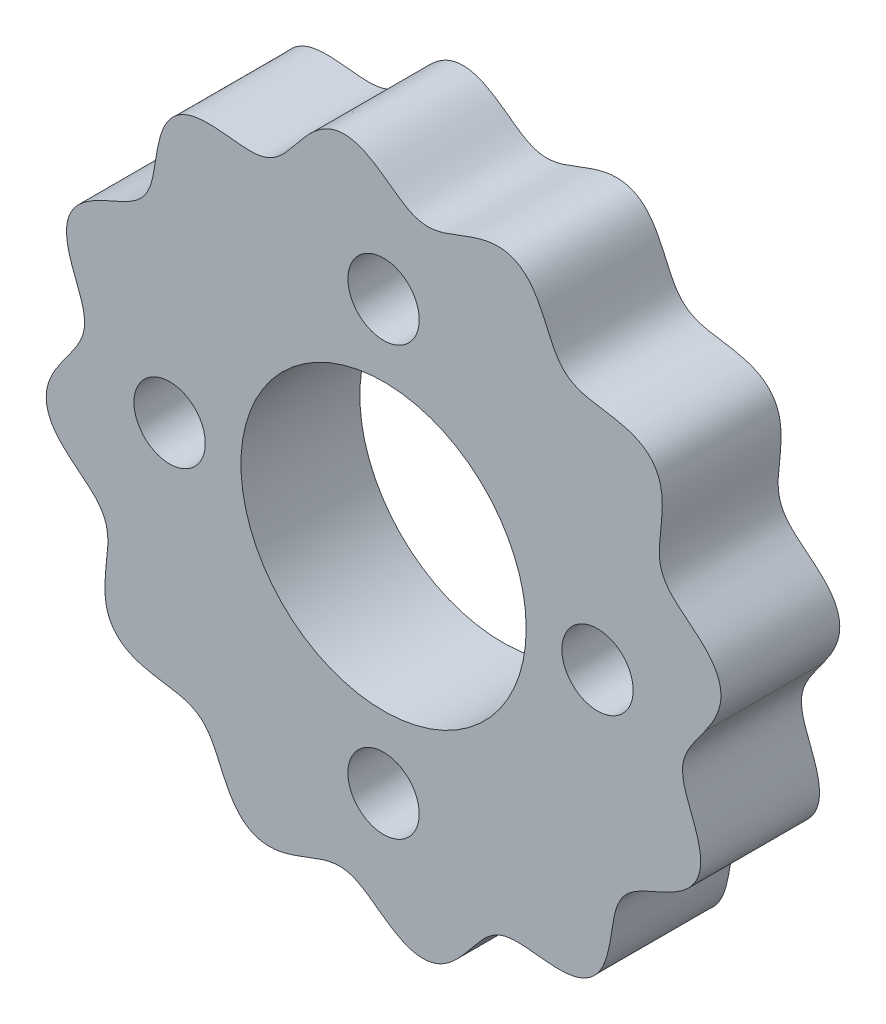
SolidWorks part; units mm, degrees
ref_plane "前视基准面" through (0, 0, 0) normal (0, 0, 1) x (1, 0, 0)
ref_plane "上视基准面" through (0, 0, 0) normal (0, 1, 0) x (1, 0, 0)
ref_plane "右视基准面" through (0, 0, 0) normal (1, 0, 0) x (0, 0, -1)
sketch "草图1" plane through (0, 0, 0) normal (0, 0, 1) x (1, 0, 0)
  circle A0 centre (0, 0) radius 12
  spline S0 degree 4 poles (26.573, -8.6341) (26.5537, -8.536) (26.5113, -8.3407) (26.4122, -7.9533) (26.2292, -7.382) (25.9846, -6.7265) (25.7182, -6.053) (25.4922, -5.4437) (25.3206, -4.8954) (25.2069, -4.4076) (25.1382, -3.8584) (25.1633, -3.2467) (25.3264, -2.6118) (25.6315, -1.9732) (25.9924, -1.3953) (26.3533, -0.8879) (26.6323, -0.5089) (26.9321, -0.0957) (27.0569, 0.0789) (27.2765, 0.396) (27.4477, 0.657) (27.6121, 0.9237) (27.7701, 1.2005) (27.9519, 1.5526) (28.1567, 2.0235) (28.3423, 2.6278) (28.4208, 3.3587) (28.3195, 4.1077) (28.0726, 4.751) (27.754, 5.2853) (27.402, 5.7395) (27.0442, 6.1277) (26.6262, 6.5264) (26.1505, 6.9354) (25.623, 7.3601) (25.0555, 7.8144) (24.5068, 8.2865) (24.0033, 8.803) (23.5859, 9.3929) (23.3119, 10.0625) (23.1946, 10.7801) (23.1899, 11.5106) (23.2475, 12.242) (23.3298, 12.9757) (23.4156, 13.786) (23.4705, 14.679) (23.4267, 15.7342) (23.1569, 16.7678) (22.6126, 17.5994) (21.8434, 18.2304) (21.0158, 18.6438) (20.1342, 18.9011) (19.2385, 19.0736) (18.4332, 19.1968) (17.7246, 19.3065) (17.0229, 19.4431) (16.3386, 19.6429) (15.6903, 19.9516) (15.1256, 20.4021) (14.6705, 20.9723) (14.3032, 21.6108) (13.9873, 22.2805) (13.6894, 22.9644) (13.3572, 23.7074) (12.9579, 24.4976) (12.3885, 25.3791) (11.6392, 26.1227) (10.7563, 26.556) (9.7906, 26.7073) (8.9022, 26.6547) (8.0357, 26.4494) (7.1919, 26.1626) (6.4375, 25.8701) (5.7603, 25.606) (5.077, 25.3667) (4.378, 25.189) (3.6584, 25.1224) (2.9416, 25.2199) (2.2614, 25.4772) (1.6264, 25.8383) (1.0219, 26.2539) (0.4276, 26.6921) (-0.2312, 27.1715) (-0.9771, 27.6656) (-1.9129, 28.1553) (-2.9429, 28.4384) (-3.9352, 28.3827) (-4.8663, 28.0321) (-5.6381, 27.5222) (-6.3017, 26.8873) (-6.8989, 26.1978) (-7.4083, 25.562) (-7.8576, 25.0032) (-8.3267, 24.4638) (-8.842, 23.9711) (-9.4335, 23.564) (-10.1059, 23.3002) (-10.8273, 23.1912) (-11.5639, 23.1923) (-12.3018, 23.2536) (-13.0431, 23.3376) (-13.8526, 23.4214) (-14.7366, 23.4706) (-15.7847, 23.4183) (-16.8033, 23.1412) (-17.6201, 22.5933) (-18.2339, 21.8325) (-18.6326, 21.0369) (-18.888, 20.1839) (-19.0615, 19.3097) (-19.1854, 18.5101) (-19.2953, 17.7915) (-19.4297, 17.0802) (-19.6253, 16.386) (-19.9274, 15.7295) (-20.3703, 15.1574) (-20.9332, 14.697) (-21.5634, 14.3277) (-22.2256, 14.0119) (-22.9022, 13.7164) (-23.6468, 13.3855) (-24.4476, 12.9866) (-25.3397, 12.421) (-26.0948, 11.6754) (-26.5388, 10.8025) (-26.7031, 9.8569) (-26.6664, 8.9884) (-26.4773, 8.1355) (-26.2027, 7.3016) (-25.9148, 6.5508) (-25.6482, 5.8708) (-25.4017, 5.1872) (-25.211, 4.4886) (-25.1244, 3.7854) (-25.1886, 3.0933) (-25.3949, 2.4518) (-25.6962, 1.8637) (-26.0443, 1.3209) (-26.3851, 0.8445) (-26.6535, 0.4799) (-26.9375, 0.0881) (-27.0592, -0.0824) (-27.2766, -0.3961) (-27.4472, -0.6562) (-27.6116, -0.9229) (-27.7695, -1.1993) (-27.9511, -1.5511) (-28.156, -2.0215) (-28.3416, -2.6252) (-28.4264, -3.4054) (-28.2941, -4.2542) (-27.9289, -5.0556) (-27.3924, -5.7762) (-26.769, -6.4074) (-26.1864, -6.9063) (-25.6744, -7.3184) (-25.3329, -7.5929) (-25.1635, -7.7318) (-25.0792, -7.8016) knots 0 0 0 0 0 0.003522 0.007043 0.014086 0.021129 0.028172 0.032574 0.036976 0.041378 0.04578 0.052068 0.058355 0.064392 0.070429 0.076467 0.079485 0.082504 0.085297 0.088091 0.090884 0.093678 0.096471 0.099265 0.104852 0.111756 0.118661 0.12494 0.131219 0.135866 0.140513 0.14516 0.149807 0.156213 0.162618 0.169024 0.175429 0.181708 0.187986 0.194329 0.200673 0.207175 0.213676 0.220178 0.22668 0.235914 0.245148 0.257333 0.263761 0.270188 0.27994 0.289691 0.29601 0.302328 0.308647 0.314965 0.321183 0.3274 0.333785 0.34017 0.346739 0.353309 0.359878 0.366447 0.375446 0.384445 0.396798 0.403077 0.409356 0.41865 0.427944 0.43435 0.440756 0.447161 0.453567 0.459845 0.466123 0.472467 0.47881 0.485312 0.491814 0.498316 0.504817 0.514051 0.523285 0.535471 0.541898 0.548326 0.558077 0.567829 0.574147 0.580466 0.586784 0.593103 0.59932 0.605538 0.611923 0.618308 0.624877 0.631446 0.638015 0.644585 0.653584 0.662583 0.674936 0.681215 0.687494 0.696788 0.706082 0.712487 0.718893 0.725299 0.731704 0.737983 0.744261 0.750604 0.756948 0.763449 0.769951 0.776453 0.782955 0.792189 0.801422 0.813608 0.819793 0.825978 0.835005 0.844032 0.850468 0.856904 0.86334 0.869776 0.876072 0.882369 0.888191 0.894014 0.899739 0.905465 0.91119 0.914053 0.916916 0.919707 0.922498 0.925289 0.928079 0.93087 0.933661 0.939243 0.946142 0.95304 0.961079 0.969118 0.976839 0.984559 0.99228 0.99614 1 1 1 1 1 construction
  spline S1 degree 4 poles (27, 0) (27.0383, 0.0539) (27.115, 0.1629) (27.2765, 0.396) (27.4477, 0.657) (27.6121, 0.9237) (27.7701, 1.2005) (27.9519, 1.5526) (28.1567, 2.0235) (28.3423, 2.6278) (28.4208, 3.3587) (28.3195, 4.1077) (28.0726, 4.751) (27.754, 5.2853) (27.402, 5.7395) (27.0442, 6.1277) (26.6262, 6.5264) (26.1505, 6.9354) (25.623, 7.3601) (25.0555, 7.8144) (24.5068, 8.2865) (24.0033, 8.803) (23.5859, 9.3929) (23.3119, 10.0625) (23.1946, 10.7801) (23.1899, 11.5106) (23.2475, 12.242) (23.3298, 12.9757) (23.4156, 13.786) (23.4705, 14.679) (23.4267, 15.7342) (23.1569, 16.7678) (22.6126, 17.5994) (21.8434, 18.2304) (21.0158, 18.6438) (20.1342, 18.9011) (19.2385, 19.0736) (18.4332, 19.1968) (17.7246, 19.3065) (17.0229, 19.4431) (16.3386, 19.6429) (15.6903, 19.9516) (15.1256, 20.4021) (14.6705, 20.9723) (14.3032, 21.6108) (13.9873, 22.2805) (13.6894, 22.9644) (13.3572, 23.7074) (12.9579, 24.4976) (12.3885, 25.3791) (11.6392, 26.1227) (10.7563, 26.556) (9.7906, 26.7073) (8.9022, 26.6547) (8.0357, 26.4494) (7.1919, 26.1626) (6.4375, 25.8701) (5.7603, 25.606) (5.077, 25.3667) (4.378, 25.189) (3.6584, 25.1224) (2.9416, 25.2199) (2.2614, 25.4772) (1.6264, 25.8383) (1.0219, 26.2539) (0.4276, 26.6921) (-0.2312, 27.1715) (-0.9771, 27.6656) (-1.9129, 28.1553) (-2.9429, 28.4384) (-3.9352, 28.3827) (-4.8663, 28.0321) (-5.6381, 27.5222) (-6.3017, 26.8873) (-6.8989, 26.1978) (-7.4083, 25.562) (-7.8576, 25.0032) (-8.3267, 24.4638) (-8.842, 23.9711) (-9.4335, 23.564) (-10.1059, 23.3002) (-10.8273, 23.1912) (-11.5639, 23.1923) (-12.3018, 23.2536) (-13.0431, 23.3376) (-13.8526, 23.4214) (-14.7366, 23.4706) (-15.7847, 23.4183) (-16.8033, 23.1412) (-17.6201, 22.5933) (-18.2339, 21.8325) (-18.6326, 21.0369) (-18.888, 20.1839) (-19.0615, 19.3097) (-19.1854, 18.5101) (-19.2953, 17.7915) (-19.4297, 17.0802) (-19.6253, 16.386) (-19.9274, 15.7295) (-20.3703, 15.1574) (-20.9332, 14.697) (-21.5634, 14.3277) (-22.2256, 14.0119) (-22.9022, 13.7164) (-23.6468, 13.3855) (-24.4476, 12.9866) (-25.3397, 12.421) (-26.0948, 11.6754) (-26.5388, 10.8025) (-26.7031, 9.8569) (-26.6664, 8.9884) (-26.4773, 8.1355) (-26.2027, 7.3016) (-25.9148, 6.5508) (-25.6482, 5.8708) (-25.4017, 5.1872) (-25.211, 4.4886) (-25.1244, 3.7854) (-25.1886, 3.0933) (-25.3949, 2.4518) (-25.6962, 1.8637) (-26.0443, 1.3209) (-26.3851, 0.8445) (-26.6535, 0.4799) (-26.8819, 0.1649) (-26.9607, 0.0552) (-27, 0) knots 0.082504 0.082504 0.082504 0.082504 0.082504 0.085297 0.088091 0.090884 0.093678 0.096471 0.099265 0.104852 0.111756 0.118661 0.12494 0.131219 0.135866 0.140513 0.14516 0.149807 0.156213 0.162618 0.169024 0.175429 0.181708 0.187986 0.194329 0.200673 0.207175 0.213676 0.220178 0.22668 0.235914 0.245148 0.257333 0.263761 0.270188 0.27994 0.289691 0.29601 0.302328 0.308647 0.314965 0.321183 0.3274 0.333785 0.34017 0.346739 0.353309 0.359878 0.366447 0.375446 0.384445 0.396798 0.403077 0.409356 0.41865 0.427944 0.43435 0.440756 0.447161 0.453567 0.459845 0.466123 0.472467 0.47881 0.485312 0.491814 0.498316 0.504817 0.514051 0.523285 0.535471 0.541898 0.548326 0.558077 0.567829 0.574147 0.580466 0.586784 0.593103 0.59932 0.605538 0.611923 0.618308 0.624877 0.631446 0.638015 0.644585 0.653584 0.662583 0.674936 0.681215 0.687494 0.696788 0.706082 0.712487 0.718893 0.725299 0.731704 0.737983 0.744261 0.750604 0.756948 0.763449 0.769951 0.776453 0.782955 0.792189 0.801422 0.813608 0.819793 0.825978 0.835005 0.844032 0.850468 0.856904 0.86334 0.869776 0.876072 0.882369 0.888191 0.894014 0.899739 0.905465 0.91119 0.914053 0.916916 0.916916 0.916916 0.916916 0.916916
  spline S2 degree 4 poles (-26.573, 8.6341) (-26.5537, 8.536) (-26.5113, 8.3407) (-26.4122, 7.9533) (-26.2292, 7.382) (-25.9846, 6.7265) (-25.7182, 6.053) (-25.4922, 5.4437) (-25.3206, 4.8954) (-25.2069, 4.4076) (-25.1382, 3.8584) (-25.1633, 3.2467) (-25.3264, 2.6118) (-25.6315, 1.9732) (-25.9924, 1.3953) (-26.3533, 0.8879) (-26.6323, 0.5089) (-26.9321, 0.0957) (-27.0569, -0.0789) (-27.2765, -0.396) (-27.4477, -0.657) (-27.6121, -0.9237) (-27.7701, -1.2005) (-27.9519, -1.5526) (-28.1567, -2.0235) (-28.3423, -2.6278) (-28.4208, -3.3587) (-28.3195, -4.1077) (-28.0726, -4.751) (-27.754, -5.2853) (-27.402, -5.7395) (-27.0442, -6.1277) (-26.6262, -6.5264) (-26.1505, -6.9354) (-25.623, -7.3601) (-25.0555, -7.8144) (-24.5068, -8.2865) (-24.0033, -8.803) (-23.5859, -9.3929) (-23.3119, -10.0625) (-23.1946, -10.7801) (-23.1899, -11.5106) (-23.2475, -12.242) (-23.3298, -12.9757) (-23.4156, -13.786) (-23.4705, -14.679) (-23.4267, -15.7342) (-23.1569, -16.7678) (-22.6126, -17.5994) (-21.8434, -18.2304) (-21.0158, -18.6438) (-20.1342, -18.9011) (-19.2385, -19.0736) (-18.4332, -19.1968) (-17.7246, -19.3065) (-17.0229, -19.4431) (-16.3386, -19.6429) (-15.6903, -19.9516) (-15.1256, -20.4021) (-14.6705, -20.9723) (-14.3032, -21.6108) (-13.9873, -22.2805) (-13.6894, -22.9644) (-13.3572, -23.7074) (-12.9579, -24.4976) (-12.3885, -25.3791) (-11.6392, -26.1227) (-10.7563, -26.556) (-9.7906, -26.7073) (-8.9022, -26.6547) (-8.0357, -26.4494) (-7.1919, -26.1626) (-6.4375, -25.8701) (-5.7603, -25.606) (-5.077, -25.3667) (-4.378, -25.189) (-3.6584, -25.1224) (-2.9416, -25.2199) (-2.2614, -25.4772) (-1.6264, -25.8383) (-1.0219, -26.2539) (-0.4276, -26.6921) (0.2312, -27.1715) (0.9771, -27.6656) (1.9129, -28.1553) (2.9429, -28.4384) (3.9352, -28.3827) (4.8663, -28.0321) (5.6381, -27.5222) (6.3017, -26.8873) (6.8989, -26.1978) (7.4083, -25.562) (7.8576, -25.0032) (8.3267, -24.4638) (8.842, -23.9711) (9.4335, -23.564) (10.1059, -23.3002) (10.8273, -23.1912) (11.5639, -23.1923) (12.3018, -23.2536) (13.0431, -23.3376) (13.8526, -23.4214) (14.7366, -23.4706) (15.7847, -23.4183) (16.8033, -23.1412) (17.6201, -22.5933) (18.2339, -21.8325) (18.6326, -21.0369) (18.888, -20.1839) (19.0615, -19.3097) (19.1854, -18.5101) (19.2953, -17.7915) (19.4297, -17.0802) (19.6253, -16.386) (19.9274, -15.7295) (20.3703, -15.1574) (20.9332, -14.697) (21.5634, -14.3277) (22.2256, -14.0119) (22.9022, -13.7164) (23.6468, -13.3855) (24.4476, -12.9866) (25.3397, -12.421) (26.0948, -11.6754) (26.5388, -10.8025) (26.7031, -9.8569) (26.6664, -8.9884) (26.4773, -8.1355) (26.2027, -7.3016) (25.9148, -6.5508) (25.6482, -5.8708) (25.4017, -5.1872) (25.211, -4.4886) (25.1244, -3.7854) (25.1886, -3.0933) (25.3949, -2.4518) (25.6962, -1.8637) (26.0443, -1.3209) (26.3851, -0.8445) (26.6535, -0.4799) (26.9375, -0.0881) (27.0592, 0.0824) (27.2766, 0.3961) (27.4472, 0.6562) (27.6116, 0.9229) (27.7695, 1.1993) (27.9511, 1.5511) (28.156, 2.0215) (28.3416, 2.6252) (28.4264, 3.4054) (28.2941, 4.2542) (27.9289, 5.0556) (27.3924, 5.7762) (26.769, 6.4074) (26.1864, 6.9063) (25.6744, 7.3184) (25.3329, 7.5929) (25.1635, 7.7318) (25.0792, 7.8016) knots 0 0 0 0 0 0.003522 0.007043 0.014086 0.021129 0.028172 0.032574 0.036976 0.041378 0.04578 0.052068 0.058355 0.064392 0.070429 0.076467 0.079485 0.082504 0.085297 0.088091 0.090884 0.093678 0.096471 0.099265 0.104852 0.111756 0.118661 0.12494 0.131219 0.135866 0.140513 0.14516 0.149807 0.156213 0.162618 0.169024 0.175429 0.181708 0.187986 0.194329 0.200673 0.207175 0.213676 0.220178 0.22668 0.235914 0.245148 0.257333 0.263761 0.270188 0.27994 0.289691 0.29601 0.302328 0.308647 0.314965 0.321183 0.3274 0.333785 0.34017 0.346739 0.353309 0.359878 0.366447 0.375446 0.384445 0.396798 0.403077 0.409356 0.41865 0.427944 0.43435 0.440756 0.447161 0.453567 0.459845 0.466123 0.472467 0.47881 0.485312 0.491814 0.498316 0.504817 0.514051 0.523285 0.535471 0.541898 0.548326 0.558077 0.567829 0.574147 0.580466 0.586784 0.593103 0.59932 0.605538 0.611923 0.618308 0.624877 0.631446 0.638015 0.644585 0.653584 0.662583 0.674936 0.681215 0.687494 0.696788 0.706082 0.712487 0.718893 0.725299 0.731704 0.737983 0.744261 0.750604 0.756948 0.763449 0.769951 0.776453 0.782955 0.792189 0.801422 0.813608 0.819793 0.825978 0.835005 0.844032 0.850468 0.856904 0.86334 0.869776 0.876072 0.882369 0.888191 0.894014 0.899739 0.905465 0.91119 0.914053 0.916916 0.919707 0.922498 0.925289 0.928079 0.93087 0.933661 0.939243 0.946142 0.95304 0.961079 0.969118 0.976839 0.984559 0.99228 0.99614 1 1 1 1 1 construction
  spline S3 degree 4 poles (-27, 0) (-27.0383, -0.0539) (-27.115, -0.1629) (-27.2765, -0.396) (-27.4477, -0.657) (-27.6121, -0.9237) (-27.7701, -1.2005) (-27.9519, -1.5526) (-28.1567, -2.0235) (-28.3423, -2.6278) (-28.4208, -3.3587) (-28.3195, -4.1077) (-28.0726, -4.751) (-27.754, -5.2853) (-27.402, -5.7395) (-27.0442, -6.1277) (-26.6262, -6.5264) (-26.1505, -6.9354) (-25.623, -7.3601) (-25.0555, -7.8144) (-24.5068, -8.2865) (-24.0033, -8.803) (-23.5859, -9.3929) (-23.3119, -10.0625) (-23.1946, -10.7801) (-23.1899, -11.5106) (-23.2475, -12.242) (-23.3298, -12.9757) (-23.4156, -13.786) (-23.4705, -14.679) (-23.4267, -15.7342) (-23.1569, -16.7678) (-22.6126, -17.5994) (-21.8434, -18.2304) (-21.0158, -18.6438) (-20.1342, -18.9011) (-19.2385, -19.0736) (-18.4332, -19.1968) (-17.7246, -19.3065) (-17.0229, -19.4431) (-16.3386, -19.6429) (-15.6903, -19.9516) (-15.1256, -20.4021) (-14.6705, -20.9723) (-14.3032, -21.6108) (-13.9873, -22.2805) (-13.6894, -22.9644) (-13.3572, -23.7074) (-12.9579, -24.4976) (-12.3885, -25.3791) (-11.6392, -26.1227) (-10.7563, -26.556) (-9.7906, -26.7073) (-8.9022, -26.6547) (-8.0357, -26.4494) (-7.1919, -26.1626) (-6.4375, -25.8701) (-5.7603, -25.606) (-5.077, -25.3667) (-4.378, -25.189) (-3.6584, -25.1224) (-2.9416, -25.2199) (-2.2614, -25.4772) (-1.6264, -25.8383) (-1.0219, -26.2539) (-0.4276, -26.6921) (0.2312, -27.1715) (0.9771, -27.6656) (1.9129, -28.1553) (2.9429, -28.4384) (3.9352, -28.3827) (4.8663, -28.0321) (5.6381, -27.5222) (6.3017, -26.8873) (6.8989, -26.1978) (7.4083, -25.562) (7.8576, -25.0032) (8.3267, -24.4638) (8.842, -23.9711) (9.4335, -23.564) (10.1059, -23.3002) (10.8273, -23.1912) (11.5639, -23.1923) (12.3018, -23.2536) (13.0431, -23.3376) (13.8526, -23.4214) (14.7366, -23.4706) (15.7847, -23.4183) (16.8033, -23.1412) (17.6201, -22.5933) (18.2339, -21.8325) (18.6326, -21.0369) (18.888, -20.1839) (19.0615, -19.3097) (19.1854, -18.5101) (19.2953, -17.7915) (19.4297, -17.0802) (19.6253, -16.386) (19.9274, -15.7295) (20.3703, -15.1574) (20.9332, -14.697) (21.5634, -14.3277) (22.2256, -14.0119) (22.9022, -13.7164) (23.6468, -13.3855) (24.4476, -12.9866) (25.3397, -12.421) (26.0948, -11.6754) (26.5388, -10.8025) (26.7031, -9.8569) (26.6664, -8.9884) (26.4773, -8.1355) (26.2027, -7.3016) (25.9148, -6.5508) (25.6482, -5.8708) (25.4017, -5.1872) (25.211, -4.4886) (25.1244, -3.7854) (25.1886, -3.0933) (25.3949, -2.4518) (25.6962, -1.8637) (26.0443, -1.3209) (26.3851, -0.8445) (26.6535, -0.4799) (26.8819, -0.1649) (26.9607, -0.0552) (27, 0) knots 0.082504 0.082504 0.082504 0.082504 0.082504 0.085297 0.088091 0.090884 0.093678 0.096471 0.099265 0.104852 0.111756 0.118661 0.12494 0.131219 0.135866 0.140513 0.14516 0.149807 0.156213 0.162618 0.169024 0.175429 0.181708 0.187986 0.194329 0.200673 0.207175 0.213676 0.220178 0.22668 0.235914 0.245148 0.257333 0.263761 0.270188 0.27994 0.289691 0.29601 0.302328 0.308647 0.314965 0.321183 0.3274 0.333785 0.34017 0.346739 0.353309 0.359878 0.366447 0.375446 0.384445 0.396798 0.403077 0.409356 0.41865 0.427944 0.43435 0.440756 0.447161 0.453567 0.459845 0.466123 0.472467 0.47881 0.485312 0.491814 0.498316 0.504817 0.514051 0.523285 0.535471 0.541898 0.548326 0.558077 0.567829 0.574147 0.580466 0.586784 0.593103 0.59932 0.605538 0.611923 0.618308 0.624877 0.631446 0.638015 0.644585 0.653584 0.662583 0.674936 0.681215 0.687494 0.696788 0.706082 0.712487 0.718893 0.725299 0.731704 0.737983 0.744261 0.750604 0.756948 0.763449 0.769951 0.776453 0.782955 0.792189 0.801422 0.813608 0.819793 0.825978 0.835005 0.844032 0.850468 0.856904 0.86334 0.869776 0.876072 0.882369 0.888191 0.894014 0.899739 0.905465 0.91119 0.914053 0.916916 0.916916 0.916916 0.916916 0.916916
extrude "凸台-拉伸1" add sketch "草图1" along normal blind 5 and the other way blind 5
sketch "草图2" plane through (0, 0, 0) normal (0, 0, 1) x (1, 0, 0)
  circle A1 centre (18, 0) radius 3
  circle A2 centre (0, -18) radius 3
  circle A3 centre (-18, 0) radius 3
  circle A4 centre (0, 18) radius 3
  point P12 (0, 0)
  dimension "D1" = 4
extrude "切除-拉伸1" cut sketch "草图2" against normal blind 10 and the other way blind 10
